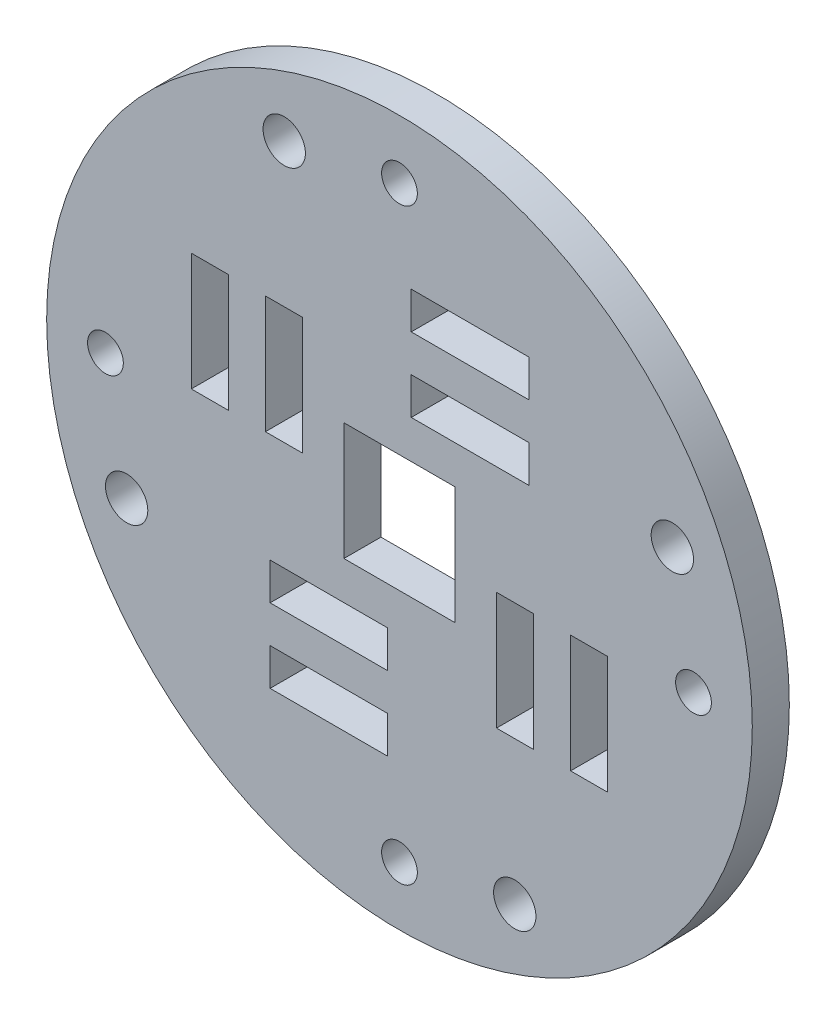
SolidWorks part; units mm, degrees
material "Hexcel AS4C (3000 Filaments)"
ref_plane "Front Plane" through (0, 0, 0) normal (0, 0, 1) x (1, 0, 0)
ref_plane "Top Plane" through (0, 0, 0) normal (0, 1, 0) x (1, 0, 0)
ref_plane "Right Plane" through (0, 0, 0) normal (1, 0, 0) x (0, 0, -1)
sketch "Sketch1" plane through (0, 0, 0) normal (0, 0, 1) x (1, 0, 0)
  circle A0 centre (0, 0) radius 38.1
  dimension "D1" = 76.2
extrude "Boss-Extrude1" add sketch "Sketch1" along normal blind 4 contours A0
sketch "Sketch2" plane through (0, 0, 4) normal (0, 0, 1) x (1, 0, 0)
  line L0 (-1.27, -10.478) -> (-13.97, -10.478)
  line L1 (10.478, -1.27) -> (14.478, -1.27)
  line L2 (10.478, -1.27) -> (10.478, -13.97)
  line L3 (10.478, -13.97) -> (14.478, -13.97)
  line L4 (14.478, -1.27) -> (14.478, -13.97)
  line L5 (18.478, -1.27) -> (22.478, -1.27)
  line L6 (18.478, -1.27) -> (18.478, -13.97)
  line L7 (18.478, -13.97) -> (22.478, -13.97)
  line L8 (22.478, -1.27) -> (22.478, -13.97)
  line L9 (-1.27, -10.478) -> (-1.27, -14.478)
  line L10 (-1.27, -14.478) -> (-13.97, -14.478)
  line L11 (-13.97, -10.478) -> (-13.97, -14.478)
  line L12 (-1.27, -18.478) -> (-13.97, -18.478)
  line L13 (-1.27, -18.478) -> (-1.27, -22.478)
  line L14 (-1.27, -22.478) -> (-13.97, -22.478)
  line L15 (-13.97, -18.478) -> (-13.97, -22.478)
  line L16 (-10.478, 1.27) -> (-10.478, 13.97)
  line L17 (-10.478, 1.27) -> (-14.478, 1.27)
  line L18 (-14.478, 1.27) -> (-14.478, 13.97)
  line L19 (-10.478, 13.97) -> (-14.478, 13.97)
  line L20 (-18.478, 1.27) -> (-18.478, 13.97)
  line L21 (-18.478, 1.27) -> (-22.478, 1.27)
  line L22 (-22.478, 1.27) -> (-22.478, 13.97)
  line L23 (-18.478, 13.97) -> (-22.478, 13.97)
  line L24 (1.27, 10.478) -> (13.97, 10.478)
  line L25 (1.27, 10.478) -> (1.27, 14.478)
  line L26 (1.27, 14.478) -> (13.97, 14.478)
  line L27 (13.97, 10.478) -> (13.97, 14.478)
  line L28 (1.27, 18.478) -> (13.97, 18.478)
  line L29 (1.27, 18.478) -> (1.27, 22.478)
  line L30 (1.27, 22.478) -> (13.97, 22.478)
  line L31 (13.97, 18.478) -> (13.97, 22.478)
  circle A0 centre (12.446, -29.464) radius 2.286
  circle A1 centre (-29.464, -12.446) radius 2.286
  circle A2 centre (-12.446, 29.464) radius 2.286
  circle A3 centre (29.464, 12.446) radius 2.286
  point P10 (0, 0)
  point P12 (14.478, -7.62)
  point P37 (0, 0)
  point P45 (0, 0)
  dimension "D8" = 4.572
  dimension "D1" = 4
  dimension "D2" = 4
  dimension "D3" = 4
  dimension "D4" = 12.7
  dimension "D5" = 14.478
  dimension "D6" = 1.27
  dimension "D9" = 21.844
  dimension "D11" = 2.032
  dimension "D7" = 4
  dimension "D10" = 4
extrude "Cut-Extrude1" cut sketch "Sketch2" against normal through all
sketch "Sketch3" plane through (0, 0, 4) normal (0, 0, 1) x (1, 0, 0)
  line L1 (-6, -6.35) -> (6, -6.35)
  line L2 (-6, -6.35) -> (-6, 6.35)
  line L3 (-6, 6.35) -> (6, 6.35)
  line L4 (6, -6.35) -> (6, 6.35)
  line L5 (-6, -6.35) -> (6, 6.35) construction
  line L6 (-6, 6.35) -> (6, -6.35) construction
  point P0 (0, 0)
  dimension "D1" = 12
  dimension "D2" = 12.7
extrude "Cut-Extrude2" cut sketch "Sketch3" against normal up to next
sketch "Sketch4" plane through (0, 0, 4) normal (0, 0, 1) x (1, 0, 0)
  circle A0 centre (0, -31.75) radius 1.9304
  circle A1 centre (31.75, 0) radius 1.9304
  circle A2 centre (0, 31.75) radius 1.9304
  circle A3 centre (-31.75, 0) radius 1.9304
  point P9 (0, 0)
  point P10 (0, 0)
  point P11 (0, 0)
  dimension "D1" = 3.8608
  dimension "D2" = 31.75
  dimension "D3" = 4
extrude "Cut-Extrude3" cut sketch "Sketch4" against normal through all
